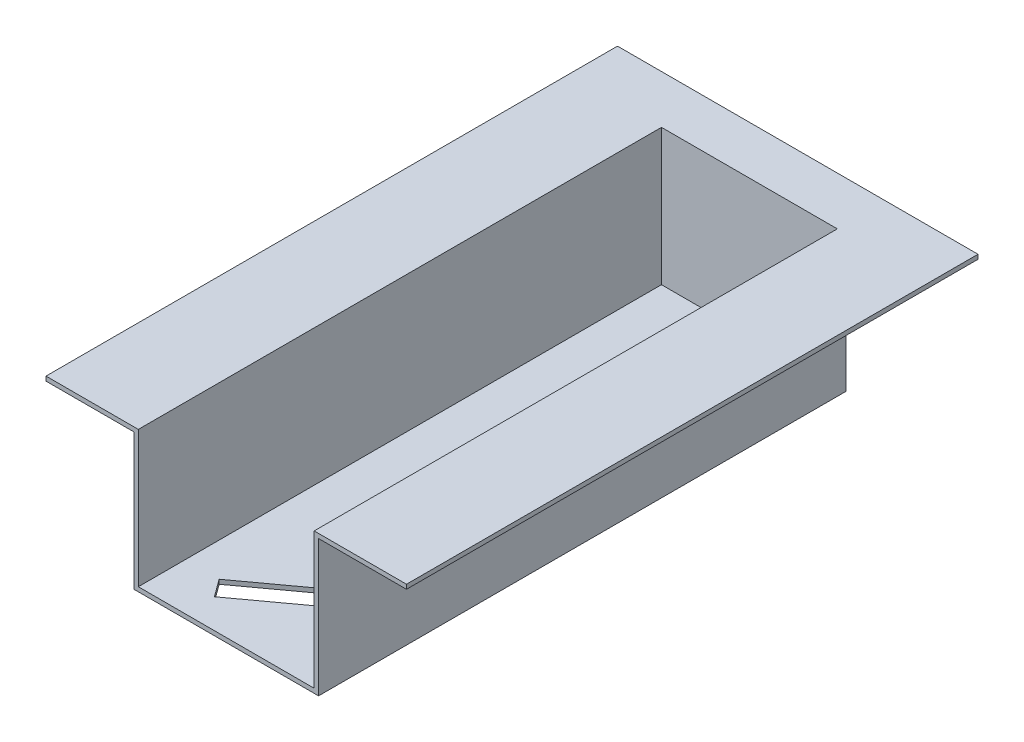
SolidWorks part; units mm, degrees
ref_plane "Front Plane" through (0, 0, 0) normal (0, 0, 1) x (1, 0, 0)
ref_plane "Top Plane" through (0, 0, 0) normal (0, 1, 0) x (1, 0, 0)
ref_plane "Right Plane" through (0, 0, 0) normal (1, 0, 0) x (0, 0, -1)
sketch "Sketch1" plane through (0, 0, 0) normal (0, 0, 1) x (1, 0, 0)
  line L0 (0, 0) -> (21, 0)
  line L1 (21, 0) -> (21, 31)
  line L2 (0, 0) -> (-21, 0)
  line L3 (-21, 0) -> (-21, 31)
  line L6 (-20, 1) -> (20, 1)
  line L9 (21, 31) -> (41, 31)
  line L10 (41, 31) -> (41, 32)
  line L11 (41, 32) -> (20, 32)
  line L12 (20, 32) -> (20, 1)
  line L13 (-21, 31) -> (-41, 31)
  line L14 (-41, 31) -> (-41, 32)
  line L15 (-41, 32) -> (-20, 32)
  line L16 (-20, 32) -> (-20, 1)
  dimension "D1" = 21
  dimension "D2" = 21
  dimension "D3" = 31
  dimension "D4" = 31
  dimension "D5" = 1
  dimension "D6" = 1
  dimension "D7" = 1
  dimension "D8" = 1
  dimension "D9" = 20
  dimension "D10" = 20
  dimension "D11" = 1
extrude "Boss-Extrude1" add sketch "Sketch1" along normal blind 120
sketch "Sketch2" plane through (0, 0, 0) normal (0, 0, 1) x (1, 0, 0)
  line L1 (-20, 32) -> (20, 32)
  line L2 (-20, 32) -> (-20, 1)
  line L3 (-20, 1) -> (20, 1)
  line L4 (20, 32) -> (20, 1)
extrude "Boss-Extrude2" add sketch "Sketch2" along normal blind 1
ref_plane "Plane1" through (0, 32, 0) normal (0, 1, 0) x (1, 0, 0)
sketch "Sketch3" plane through (0, 32, 0) normal (0, 1, 0) x (1, 0, 0)
  line L1 (-41, 0) -> (41, 0)
  line L2 (-41, 0) -> (-41, 10)
  line L3 (-41, 10) -> (41, 10)
  line L4 (41, 0) -> (41, 10)
  dimension "D1" = 82
  dimension "D2" = 10
extrude "Boss-Extrude3" add sketch "Sketch3" against normal blind 1
sketch "Sketch5" plane through (0, 0, 0) normal (0, -1, 0) x (1, 0, 0)
  line L0 (-12.29, 109.3244) -> (12.4207, 91.2816)
  line L1 (12.4207, 91.2816) -> (-10.2812, 60.1898)
  line L2 (-10.2812, 60.1898) -> (12.4207, 40.6835)
  line L3 (12.4207, 40.6835) -> (-7.3205, 17.7082)
  line L4 (-12.29, 109.3244) -> (-9.3763, 113.315)
  line L5 (-9.3763, 113.315) -> (17.7494, 93.5089)
  line L6 (17.7494, 93.5089) -> (-5.622, 60.1898)
  line L7 (-5.622, 60.1898) -> (17.7494, 40.6835)
  line L8 (17.7494, 40.6835) -> (-4.0236, 14.5964)
  line L9 (-4.0236, 14.5964) -> (-7.3205, 17.7082)
extrude "Cut-Extrude1" cut sketch "Sketch5" against normal up to next
